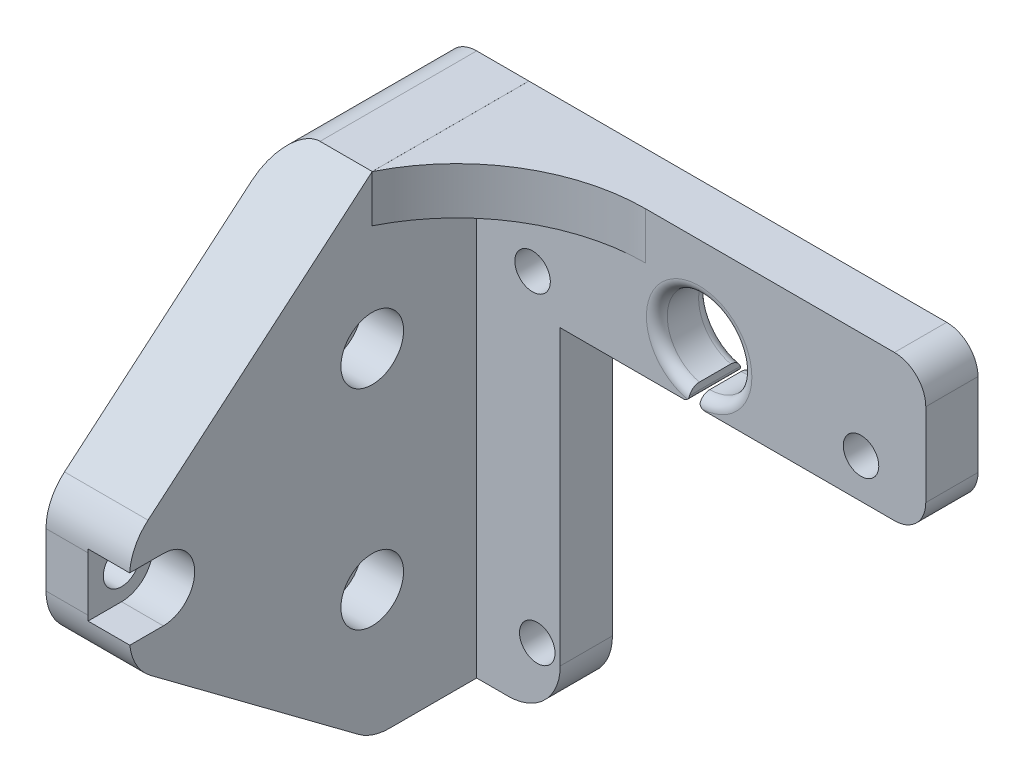
SolidWorks part; units mm, degrees
material "ABS"
ref_plane "Front Plane" through (0, 0, 0) normal (0, 0, 1) x (1, 0, 0)
ref_plane "Top Plane" through (0, 0, 0) normal (0, 1, 0) x (1, 0, 0)
ref_plane "Right Plane" through (0, 0, 0) normal (1, 0, 0) x (0, 0, -1)
ref_plane "Plane5" through (60, 0, 0) normal (1, 0, 0) x (0, 0, -1)
sketch "Sketch50" plane through (60, 0, 0) normal (1, 0, 0) x (0, 0, -1)
  line L0 (-38.2349, -28) -> (-38.2349, -38)
  line L1 (0, -55.3249) -> (-15, -55.3249)
  line L2 (0, -8.3249) -> (-15, -8.3249)
  line L4 (0, -55.3249) -> (0, -8.3249)
  line L5 (-15, -2.0171) -> (-15, -57.8143) construction
  line L9 (-38.2349, -28) -> (-15, -8.3249)
  line L10 (-38.2349, -38) -> (-15, -55.3249)
  circle A0 centre (-35, -33) radius 1.75
  circle A1 centre (-15, -23) radius 1.75
  circle A2 centre (-15, -43) radius 1.75
  dimension "D1" = 3.5
  dimension "D2" = 3.5
  dimension "D3" = 3.5
  dimension "D4" = 20
  dimension "D5" = 20
  dimension "D6" = 47
  dimension "D7" = 15
  dimension "D8" = 10
extrude "Extrude1" add sketch "Sketch50" along normal blind 8 separate body
sketch "Sketch52" plane through (0, 0, 0) normal (0, 0, -1) x (-1, 0, 0)
  line L0 (-60.0211, -55.3284) -> (-60.0211, -8.3284)
  line L1 (-111, -8.3284) -> (-111, -22.2806)
  line L2 (-60.0211, -8.3284) -> (-111, -8.3284)
  line L3 (-76, -22.2806) -> (-111, -22.2806)
  line L4 (-60.0211, -55.3284) -> (-76, -55.3284)
  line L5 (-76, -55.3249) -> (-76, -8.3249)
  line L6 (-76, -55.3284) -> (-76, -22.2806)
  circle A0 centre (-89.3, -17.2) radius 4.05
  circle A1 centre (-73.3515, -18.9313) radius 1.7
  circle A2 centre (-104.8, -18.5) radius 1.7
  circle A3 centre (-73.8015, -49.5086) radius 1.7
  point P3 (-113, -87.5802)
  point P9 (-74.0211, -54.9585)
  point P10 (-74.0211, -7.7617)
  dimension "D2" = 47
  dimension "D4" = 3.4
  dimension "D1" = 8
extrude "Extrude2" add sketch "Sketch52" against normal blind 5
fillet "Fillet1" radius 3 2 edges at (111, -22.2806, 2.5) (111, -8.3284, 2.5)
fillet "Fillet2" radius 5 1 edges at (76, -55.3284, 2.5)
sketch "Sketch54" plane through (0, -8.3284, 0) normal (0, 1, 0) x (1, 0, 0)
  line L0 (68, -5) -> (108, -5) construction
  line L1 (68, -15) -> (68, -5)
  line L2 (68, -15) -> (68, -38.2349) construction
  line L3 (68, 0) -> (68, -15) construction
  line L4 (68, -5) -> (84.1795, -5)
  arc A0 (84.1795, -5) -> (68, -15) centre (84.1795, -23.0887) ccw
extrude "Extrude3" add sketch "Sketch54" against normal blind 4.5
fillet "Fillet4" radius 5 3 edges at (64, -28, 38.2349) (64, -38, 38.2349) (64, -55.3249, 15)
fillet "Fillet5" radius 3 1 edges at (60, -8.3249, 7.5)
sketch "Sketch55" plane through (68, 0, 0) normal (1, 0, 0) x (0, 0, -1)
  line L0 (-35, -30) -> (-38.7879, -30)
  line L1 (-38.7879, -30) -> (-38.7879, -36)
  line L2 (-35, -36) -> (-38.7879, -36)
  arc A0 (-35, -36) -> (-35, -30) centre (-35, -33) ccw
  circle A1 centre (-15, -23) radius 3
  circle A2 centre (-15, -43) radius 3
  dimension "D1" = 6
  dimension "D2" = 6
  dimension "D3" = 6
extrude "Cut-Extrude3" cut sketch "Sketch55" against normal blind 4
fillet "Fillet6" radius 1 2 edges at (89.3, -13.15, 5) (89.3, -13.15, 0)
sketch "Sketch56" plane through (0, 0, 0) normal (0, 0, -1) x (-1, 0, 0)
  line L0 (-108, -22.2806) -> (-76, -22.2806) construction
  line L1 (-89.3173, -23.6005) -> (-88.3204, -23.6005)
  line L2 (-89.3173, -23.6005) -> (-89.3173, -20.9607)
  line L3 (-89.3173, -20.9607) -> (-88.3204, -20.9607)
  line L4 (-88.3204, -23.6005) -> (-88.3204, -20.9607)
  line L5 (-89.3173, -23.6005) -> (-88.3204, -20.9607) construction
  line L6 (-89.3173, -20.9607) -> (-88.3204, -23.6005) construction
  point P0 (-88.8189, -22.2806)
extrude "Cut-Extrude4" cut sketch "Sketch56" against normal up to surface (5 mm away) up to face at (89.3, -12.15, 5)
fillet "Fillet7" radius 0.5 2 edges at (88.3204, -22.2806, 2.5) (89.3173, -22.2806, 2.5)
